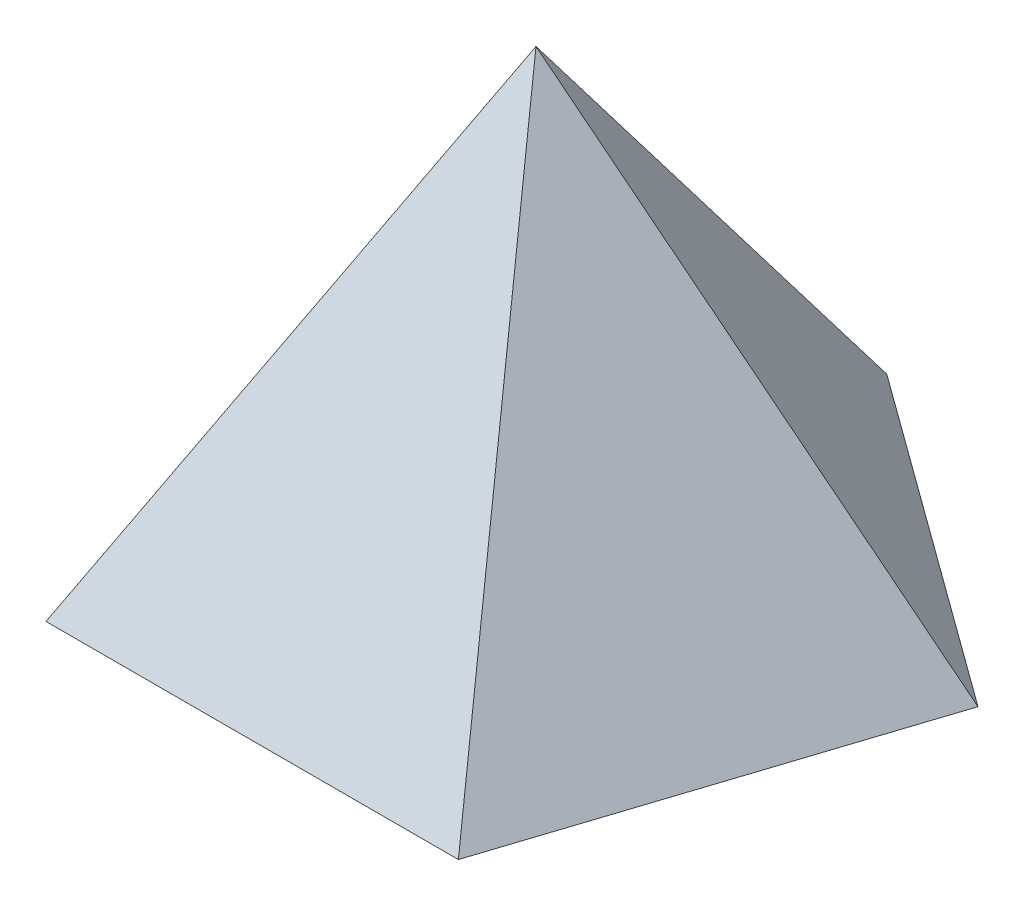
SolidWorks part; units mm, degrees
ref_plane "Front Plane" through (0, 0, 0) normal (0, 0, 1) x (1, 0, 0)
ref_plane "Top Plane" through (0, 0, 0) normal (0, 1, 0) x (1, 0, 0)
ref_plane "Right Plane" through (0, 0, 0) normal (1, 0, 0) x (0, 0, -1)
sketch "Sketch1" plane through (0, 0, 0) normal (0, 1, 0) x (1, 0, 0)
  line L1 (0, 10.8033) -> (-10.2745, 3.3384)
  line L2 (-10.2745, 3.3384) -> (-6.35, -8.74)
  line L3 (-6.35, -8.74) -> (6.35, -8.74)
  line L4 (6.35, -8.74) -> (10.2745, 3.3384)
  line L5 (10.2745, 3.3384) -> (0, 10.8033)
  circle A0 centre (0, 0) radius 8.74 construction
  point P1 (0, 0)
  dimension "D1" = 12.7
extrude "Boss-Extrude1" add sketch "Sketch1" along normal blind 25.4 draft 31.717
mirror "Mirror1" [suppressed]
equation "\"angle\"= arccos ( - sqr ( 5 ) / 5 )"
equation "\"theta\"= 90 - \"angle\" / 2"
equation "\"side\"=0.5"
equation "\"D1@Sketch1\"=\"side\""
equation "\"D3@Boss-Extrude1\"=\"theta\""
equation "\"D1@Boss-Extrude1\"=\"side\"*2"
